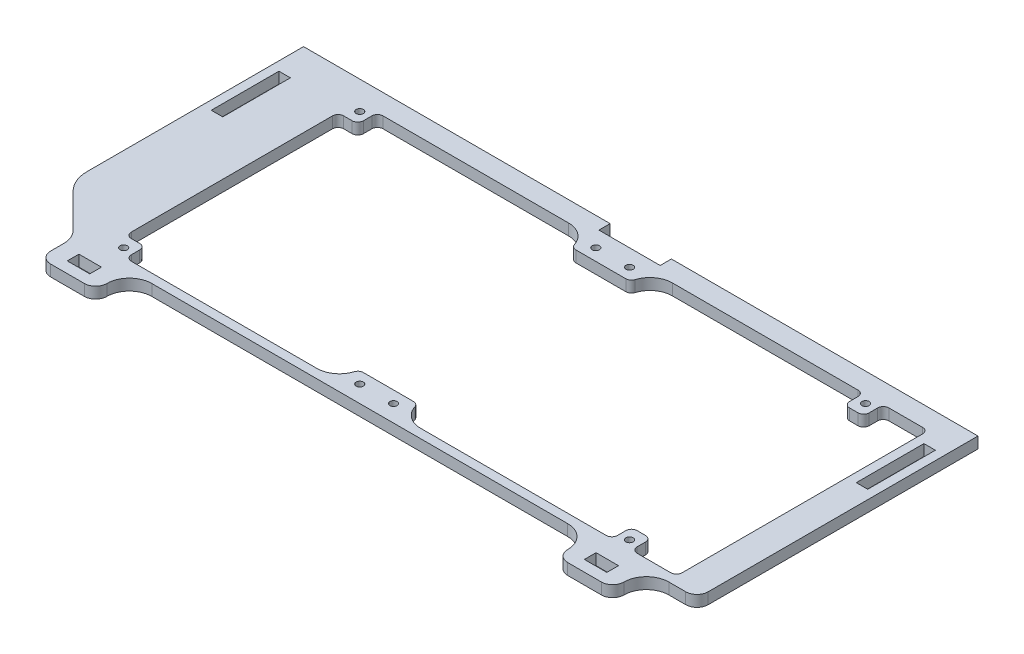
SolidWorks part; units mm, degrees
ref_plane "Front Plane" through (0, 0, 0) normal (0, 0, 1) x (1, 0, 0)
ref_plane "Top Plane" through (0, 0, 0) normal (0, 1, 0) x (1, 0, 0)
ref_plane "Right Plane" through (0, 0, 0) normal (1, 0, 0) x (0, 0, -1)
sketch "Sketch1" plane through (0, 0, 0) normal (0, 1, 0) x (1, 0, 0)
  line L1 (127.5, -60) -> (-127.5, -60)
  line L2 (127.5, -60) -> (127.5, 60)
  line L3 (127.5, 60) -> (-127.5, 60)
  line L4 (-127.5, -60) -> (-127.5, 60)
  line L5 (127.5, -60) -> (-127.5, 60) construction
  line L6 (127.5, 60) -> (-127.5, -60) construction
  line L7 (-112.5, 52.5) -> (-7.5, 52.5) construction
  line L8 (-7.5, 52.5) -> (-7.5, -52.5) construction
  line L9 (-7.5, -52.5) -> (-112.5, -52.5) construction
  line L10 (-112.5, -52.5) -> (-112.5, 52.5) construction
  line L11 (7.5, 52.5) -> (112.5, 52.5) construction
  line L12 (112.5, 52.5) -> (112.5, -52.5) construction
  line L13 (112.5, -52.5) -> (7.5, -52.5) construction
  line L14 (7.5, -52.5) -> (7.5, 52.5) construction
  line L15 (7.5, 52.5) -> (-7.5, 52.5) construction
  line L16 (112.5, 52.5) -> (127.5, 52.5) construction
  line L17 (-112.5, 52.5) -> (-127.5, 52.5) construction
  line L18 (-7.5, 52.5) -> (7.5, -52.5) construction
  circle A0 centre (-112.5, 52.5) radius 1.6
  circle A1 centre (-112.5, -52.5) radius 1.6
  circle A2 centre (-7.5, -52.5) radius 1.6
  circle A3 centre (-7.5, 52.5) radius 1.6
  circle A4 centre (7.5, 52.5) radius 1.6
  circle A5 centre (112.5, 52.5) radius 1.6
  circle A6 centre (112.5, -52.5) radius 1.6
  circle A7 centre (7.5, -52.5) radius 1.6
  point P0 (0, 0)
  dimension "D3" = 3.2
  dimension "D1" = 120
  dimension "D2" = 105
  dimension "D4" = 15
base flange "Base-Flange1" sketch "Sketch1" thickness 5 reverse thickness direction no parameters "D1"=0.7366
sketch "Sketch6" plane through (0, 0, 0) normal (0, 1, 0) x (1, 0, 0)
  line L0 (-108.125, 56) -> (-108.125, 47.25)
  line L1 (-108.125, 47.25) -> (-116.875, 47.25)
  line L2 (-116.875, 47.25) -> (-116.875, -47.25)
  line L3 (-116.875, -47.25) -> (-108.125, -47.25)
  line L4 (-108.125, -47.25) -> (-108.125, -56)
  line L5 (-108.125, -56) -> (-13.625, -56)
  line L6 (-13.625, -56) -> (-13.625, -47.25)
  line L7 (-13.625, -47.25) -> (13.625, -47.25)
  line L8 (13.625, -47.25) -> (13.625, -56)
  line L9 (13.625, -56) -> (108.125, -56)
  line L10 (108.125, -56) -> (108.125, -47.25)
  line L11 (108.125, -47.25) -> (116.875, -47.25)
  line L12 (116.875, -47.25) -> (116.875, 47.25)
  line L13 (116.875, 47.25) -> (108.125, 47.25)
  line L14 (108.125, 47.25) -> (108.125, 56)
  line L15 (108.125, 56) -> (13.625, 56)
  line L16 (13.625, 56) -> (13.625, 47.25)
  line L17 (13.625, 47.25) -> (-13.625, 47.25)
  line L18 (-13.625, 47.25) -> (-13.625, 56)
  line L19 (-13.625, 56) -> (-108.125, 56)
  line L20 (-127.5, 0) -> (-116.875, 0) construction
  line L21 (-127.5, 60) -> (-127.5, -60) construction
  line L22 (116.875, 0) -> (127.5, 0) construction
  line L23 (127.5, -60) -> (127.5, 60) construction
  line L24 (127.5, 60) -> (-127.5, 60) construction
  line L25 (60.875, 56) -> (60.875, 60) construction
  line L26 (-13.625, 51.625) -> (0, 51.625) construction
  line L27 (0, 51.625) -> (13.625, 51.625) construction
  line L28 (-112.5, 52.5) -> (-112.5, 47.25) construction
  dimension "D1" = 4
  dimension "D2" = 12.75
extrude "Cut-Extrude1" cut sketch "Sketch6" against normal up to next
sketch "Sketch9" plane through (0, 0, 0) normal (0, 1, 0) x (1, 0, 0)
  line L0 (-127.5, 60) -> (-150, 60) construction
  line L1 (-150, 60) -> (-150, -31.2868)
  line L3 (-127.5, -60) -> (127.5, -60) construction
  line L4 (-127.5, 60) -> (-127.5, -60)
  line L5 (0, -60) -> (0, 60) construction
  line L6 (127.5, 60) -> (-127.5, 60) construction
  line L11 (-143.45, 50.05) -> (-143.45, 60) construction
  line L12 (-146, 19.95) -> (-140.9, 19.95)
  line L13 (-146, 19.95) -> (-146, 50.05)
  line L14 (-146, 50.05) -> (-140.9, 50.05)
  line L15 (-140.9, 19.95) -> (-140.9, 50.05)
  line L16 (-146, 19.95) -> (-140.9, 50.05) construction
  line L17 (-146, 50.05) -> (-140.9, 19.95) construction
  line L18 (-143.45, 19.95) -> (-143.45, 10) construction
  line L19 (143.45, 19.95) -> (143.45, 10) construction
  line L20 (146, 50.05) -> (140.9, 19.95) construction
  line L21 (146, 19.95) -> (140.9, 50.05) construction
  line L22 (143.45, 50.05) -> (143.45, 60) construction
  line L23 (140.9, 19.95) -> (140.9, 50.05)
  line L24 (146, 50.05) -> (140.9, 50.05)
  line L25 (146, 19.95) -> (146, 50.05)
  line L26 (146, 19.95) -> (140.9, 19.95)
  line L27 (127.5, 60) -> (127.5, -60)
  line L29 (150, 60) -> (150, -55)
  line L30 (127.5, 60) -> (150, 60) construction
  line L31 (-150, 60) -> (-150, 65)
  line L32 (-150, 65) -> (-13.625, 65)
  line L33 (-13.625, 65) -> (-13.625, 60)
  line L34 (-13.625, 60) -> (-127.5, 60)
  line L35 (-13.625, 47.25) -> (-13.625, 56) construction
  line L36 (150, 60) -> (150, 65)
  line L37 (150, 65) -> (13.625, 65)
  line L38 (13.625, 60) -> (127.5, 60)
  line L39 (13.625, 65) -> (13.625, 60)
  line L40 (-145.6066, -41.8934) -> (-127.5, -60)
  line L41 (-145.6066, -41.8934) -> (-145.6066, -60) construction
  line L42 (-145.6066, -60) -> (-127.5, -60) construction
  line L44 (127.5, -60) -> (145, -60)
  arc A0 (-150, -31.2868) -> (-145.6066, -41.8934) centre (-135, -31.2868) ccw
  arc A5 (145, -60) -> (150, -55) centre (145, -55) ccw
  point P16 (-143.45, 35)
  point P34 (143.45, 35)
  dimension "D7" = 15
  dimension "D8" = 5
  dimension "D1" = 50
  dimension "D2" = 30.1
  dimension "D3" = 5.1
  dimension "D4" = 150
  dimension "D5" = 5
  dimension "D6" = 4
extrude "Boss-Extrude1" add sketch "Sketch9" against normal up to surface (5 mm away) up to face at (0, -5, 0)
sketch "Sketch10" plane through (0, 0, 0) normal (0, 1, 0) x (1, 0, 0)
  line L0 (127.5, -60) -> (127.5, -75)
  line L1 (127.5, -75) -> (102.5, -75)
  line L2 (102.5, -75) -> (102.5, -60)
  line L3 (-127.5, -60) -> (145, -60) construction
  line L4 (102.5, -60) -> (127.5, -60)
  line L5 (120, -64.9) -> (110, -64.9)
  line L6 (110, -64.9) -> (110, -70.1)
  line L7 (110, -70.1) -> (120, -70.1)
  line L8 (120, -70.1) -> (120, -64.9)
  line L9 (115, -64.9) -> (115, -60) construction
  line L10 (115, -70.1) -> (115, -75) construction
  line L11 (0, -47.25) -> (0, 47.25) construction
  line L12 (-13.625, -47.25) -> (13.625, -47.25) construction
  line L13 (13.625, 47.25) -> (-13.625, 47.25) construction
  line L14 (-115, -70.1) -> (-115, -75) construction
  line L15 (-115, -64.9) -> (-115, -60) construction
  line L16 (-120, -70.1) -> (-120, -64.9)
  line L17 (-110, -70.1) -> (-120, -70.1)
  line L18 (-110, -64.9) -> (-110, -70.1)
  line L19 (-120, -64.9) -> (-110, -64.9)
  line L20 (-102.5, -60) -> (-127.5, -60)
  line L21 (-102.5, -75) -> (-102.5, -60)
  line L22 (-127.5, -75) -> (-102.5, -75)
  line L23 (-127.5, -60) -> (-127.5, -75)
  dimension "D1" = 5.2
  dimension "D2" = 15
  dimension "D3" = 10
  dimension "D4" = 25
extrude "Boss-Extrude2" add sketch "Sketch10" against normal up to surface (5 mm away)
fillet "Fillet1" radius 5 4 edges at (127.5, -2.5, 75) (102.5, -2.5, 75) (-127.5, -2.5, 75) (-102.5, -2.5, 75)
fillet "Fillet2" radius 2.5 16 edges at (108.125, -2.5, 56) (108.125, -2.5, 47.25) (116.875, -2.5, 47.25) (-13.625, -2.5, 47.25) (13.625, -2.5, 47.25) (-116.875, -2.5, 47.25) (-108.125, -2.5, 47.25) (-108.125, -2.5, 56) (-108.125, -2.5, -56) (-116.875, -2.5, -47.25) (-108.125, -2.5, -47.25) (13.625, -2.5, -47.25) (-13.625, -2.5, -47.25) (108.125, -2.5, -56) (116.875, -2.5, -47.25) (108.125, -2.5, -47.25)
fillet "Fillet3" radius 10 26 edges at (127.5, -2.5, 60) (102.5, -2.5, 60) (102.5, 0, 65) (127.5, -5, 65) (-102.5, -2.5, 60) (-102.5, -5, 65) (-102.5, 0, 65) (127.5, 0, 65) (102.5, -5, 65) (-13.625, 0, -52.875) (13.625, 0, 52.875) (-13.625, -5, 52.875) (13.625, -5, -52.875) (-13.625, -2.5, 49.75) (13.625, -2.5, 49.75) (13.625, -2.5, -49.75) (-13.625, -2.5, -49.75) (-13.625, -2.5, -56) (13.625, -2.5, -56) (13.625, -2.5, 56) (-13.625, -2.5, 56) (-13.625, 0, 52.875) (13.625, 0, -52.875) (-13.625, -5, -52.875) (13.625, -5, 52.875) (-127.5, -2.5, 60)
sketch "Sketch11" plane through (0, 0, 0) normal (0, 1, 0) x (1, 0, 0)
  line L0 (116.875, 49.75) -> (116.875, 53.5)
  line L2 (116.875, -44.75) -> (116.875, 44.75) construction
  line L3 (119.375, 56) -> (134.375, 56)
  line L4 (105.625, 56) -> (23.0492, 56) construction
  line L5 (136.875, 53.5) -> (136.875, -53.5)
  line L6 (116.875, -44.75) -> (116.875, 44.75)
  line L8 (119.375, -56) -> (134.375, -56)
  line L9 (116.875, -53.5) -> (116.875, -49.75)
  line L12 (110.625, -47.25) -> (114.375, -47.25) construction
  line L13 (23.0492, -56) -> (105.625, -56) construction
  arc A1 (116.875, 53.5) -> (119.375, 56) centre (119.375, 53.5) cw
  arc A2 (116.875, 49.75) -> (114.375, 47.25) centre (114.375, 49.75) cw
  arc A3 (116.875, 44.75) -> (114.375, 47.25) centre (114.375, 44.75) ccw construction
  arc A4 (134.375, 56) -> (136.875, 53.5) centre (134.375, 53.5) cw
  arc A5 (116.875, 44.75) -> (114.375, 47.25) centre (114.375, 44.75) ccw
  arc A8 (114.375, -47.25) -> (116.875, -44.75) centre (114.375, -44.75) ccw construction
  arc A9 (114.375, -47.25) -> (116.875, -44.75) centre (114.375, -44.75) ccw
  arc A10 (134.375, -56) -> (136.875, -53.5) centre (134.375, -53.5) ccw
  arc A11 (119.375, -56) -> (116.875, -53.5) centre (119.375, -53.5) cw
  arc A12 (116.875, -49.75) -> (114.375, -47.25) centre (114.375, -49.75) ccw
  dimension "D2" = 20
extrude "Cut-Extrude2" cut sketch "Sketch11" against normal through all
sketch "Bend-Lines1" [suppressed] plane through (0, 0, 0) normal (0, 1, 0) x (1, 0, 0)
sketch "Bounding-Box1" [suppressed] plane through (0, 0, 0) normal (0, 1, 0) x (1, 0, 0)
sheet metal parameters "Sheet-Metal1" thickness 5 parameters "D1"=0.7366
flat pattern "Flat-Pattern1" [suppressed]
sketch "Bend-Lines2" plane through (0, 0, 0) normal (0, 1, 0) x (1, 0, 0)
sketch3d "Bounding-Box2" [suppressed]
  line L0 (-120, -60, 0) -> (120, -60, 0) construction
  line L1 (-120, 60, 0) -> (120, 60, 0) construction
  line L2 (-120, -60, 0) -> (-120, 60, 0) construction
  line L3 (120, -60, 0) -> (120, 60, 0) construction
sheet metal parameters "Sheet-Metal2" thickness 5 parameters "D1"=0.7366
flat pattern "Flat-Pattern1"
sketch "Bend-Lines2" plane through (0, 0, 0) normal (0, 1, 0) x (1, 0, 0)
sketch3d "Bounding-Box2" [suppressed]
  line L0 (127.5, -60, 0) -> (-127.5, -60, 0) construction
  line L1 (127.5, 60, 0) -> (-127.5, 60, 0) construction
  line L2 (127.5, -60, 0) -> (127.5, 60, 0) construction
  line L3 (-127.5, -60, 0) -> (-127.5, 60, 0) construction
sheet metal parameters "Sheet-Metal3" thickness 5 parameters "D1"=0.7366
flat pattern "Flat-Pattern1"
sketch "Bend-Lines2" plane through (0, 0, 0) normal (0, 1, 0) x (1, 0, 0)
sketch3d "Bounding-Box2" [suppressed]
  line L0 (-157.5, -60, 0) -> (157.5, -60, 0) construction
  line L1 (-157.5, 65, 0) -> (157.5, 65, 0) construction
  line L2 (-157.5, -60, 0) -> (-157.5, 65, 0) construction
  line L3 (157.5, -60, 0) -> (157.5, 65, 0) construction
sheet metal parameters "Sheet-Metal4" thickness 5 parameters "D1"=0.7366
flat pattern "Flat-Pattern1"
sketch "Bend-Lines2" plane through (0, 0, 0) normal (0, 1, 0) x (1, 0, 0)
sketch3d "Bounding-Box2" [suppressed]
  line L0 (-150, -75, 0) -> (150, -75, 0) construction
  line L1 (-150, 65, 0) -> (150, 65, 0) construction
  line L2 (-150, -75, 0) -> (-150, 65, 0) construction
  line L3 (150, -75, 0) -> (150, 65, 0) construction
sheet metal parameters "Sheet-Metal5" thickness 5 parameters "D1"=0.7366
flat pattern "Flat-Pattern1"
sketch "Bend-Lines2" plane through (0, 0, 0) normal (0, 1, 0) x (1, 0, 0)
sketch3d "Bounding-Box2" [suppressed]
  line L0 (-150, -75, 0) -> (150, -75, 0) construction
  line L1 (-150, 65, 0) -> (150, 65, 0) construction
  line L2 (-150, -75, 0) -> (-150, 65, 0) construction
  line L3 (150, -75, 0) -> (150, 65, 0) construction
